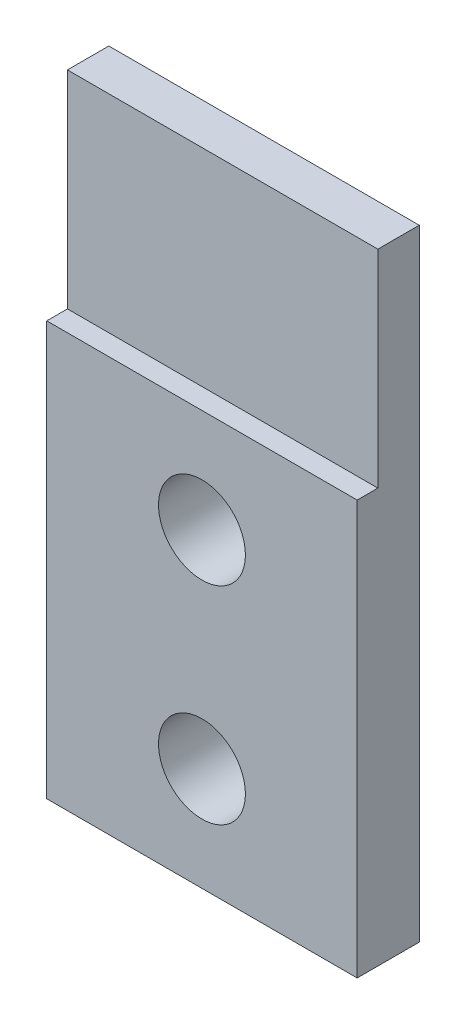
SolidWorks part; units mm, degrees
ref_plane "Спереди" through (0, 0, 0) normal (0, 0, 1) x (1, 0, 0)
ref_plane "Сверху" through (0, 0, 0) normal (0, 1, 0) x (1, 0, 0)
ref_plane "Справа" through (0, 0, 0) normal (1, 0, 0) x (0, 0, -1)
sketch "Эскиз1" plane through (0, 0, 0) normal (0, 0, 1) x (1, 0, 0)
  line L1 (-15, -30) -> (15, -30)
  line L2 (-15, -30) -> (-15, 30)
  line L3 (-15, 30) -> (15, 30)
  line L4 (15, -30) -> (15, 30)
  line L5 (-15, -30) -> (15, 30) construction
  line L6 (-15, 30) -> (15, -30) construction
  circle A0 centre (0, -20) radius 4.2
  circle A1 centre (0, 0) radius 4.2
  point P0 (0, 0)
extrude "Бобышка-Вытянуть1" add sketch "Эскиз1" along normal blind 6
sketch "Эскиз2" plane through (15, 0, 0) normal (-1, 0, 0) x (0, 0, 1)
  line L0 (6, 30) -> (6, 10)
  line L2 (6, 10) -> (4, 10)
  line L4 (6, 30) -> (4, 30)
  line L5 (4, 30) -> (4, 10)
  line L7 (6, 30) -> (0, 30) construction
  line L8 (6, -30) -> (6, 30) construction
  point P2 (0, 0)
  point P3 (0, 0)
  point P4 (5, 30)
  point P6 (3.7909, 10.4431)
  point P7 (3.7494, 30)
  point P10 (6, 30.35)
  point P12 (6, 30)
  point P14 (6, 30)
extrude "Вырез-Вытянуть1" cut sketch "Эскиз2" along normal through all
